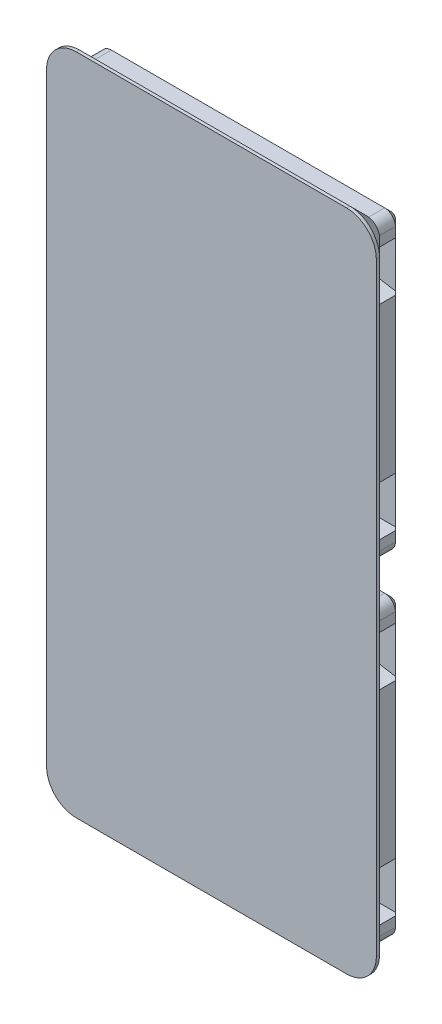
SolidWorks part; units mm, degrees
ref_plane "Front Plane" through (0, 0, 0) normal (0, 0, 1) x (1, 0, 0)
ref_plane "Top Plane" through (0, 0, 0) normal (0, 1, 0) x (1, 0, 0)
ref_plane "Right Plane" through (0, 0, 0) normal (1, 0, 0) x (0, 0, -1)
sketch "Sketch1" plane through (0, 0, 0) normal (0, 0, 1) x (1, 0, 0)
  line L1 (18.55, 18.55) -> (-18.55, 18.55)
  line L2 (18.55, 18.55) -> (18.55, -18.55)
  line L3 (18.55, -18.55) -> (-18.55, -18.55)
  line L4 (-18.55, 18.55) -> (-18.55, -18.55)
  line L5 (18.55, 18.55) -> (-18.55, -18.55) construction
  line L6 (18.55, -18.55) -> (-18.55, 18.55) construction
  point P0 (0, 0)
  dimension "D1" = 37.1
extrude "Boss-Extrude1" add sketch "Sketch1" along normal blind 2.6
sketch "Sketch2" plane through (0, 0, 2.6) normal (0, 0, 1) x (1, 0, 0)
  line L1 (-20.75, 20.75) -> (20.75, 20.75)
  line L2 (-20.75, 20.75) -> (-20.75, -20.75)
  line L3 (-20.75, -20.75) -> (20.75, -20.75)
  line L4 (20.75, 20.75) -> (20.75, -20.75)
  line L5 (-20.75, 20.75) -> (20.75, -20.75) construction
  line L6 (-20.75, -20.75) -> (20.75, 20.75) construction
  point P0 (0, 0)
  dimension "D1" = 41.5
extrude "Boss-Extrude2" add sketch "Sketch2" along normal blind 2.4
sketch "Sketch8" plane through (0, 0, 2.6) normal (0, 0, -1) x (-1, 0, 0)
  line L0 (-18.55, 18.55) -> (-18.55, 5.0094) construction
  line L1 (-18.55, -18.55) -> (-18.55, 18.55) construction
  line L2 (-14.8915, 10.3) -> (-18.55, 9.7)
  line L8 (12.7, 15.95) -> (-12.7, 15.95) construction
  line L9 (12.7, 9.45) -> (-12.7, 9.45) construction
  line L11 (-12.7, 15.95) -> (-18.55, 15.95)
  line L12 (-12.7, 12.7) -> (-12.7, -12.7)
  line L13 (-12.7, -12.7) -> (12.7, -12.7)
  line L14 (12.7, -12.7) -> (12.7, 12.7)
  line L15 (12.7, 12.7) -> (-12.7, 12.7)
  line L16 (-12.7, 9.45) -> (-12.7, -12.7) construction
  line L17 (-12.7, -12.7) -> (12.7, -12.7) construction
  line L18 (12.7, -12.7) -> (12.7, 12.7) construction
  line L19 (12.7, 12.7) -> (-12.7, 12.7) construction
  line L22 (-18.55, 15.95) -> (-18.55, 9.7)
  arc A0 (-12.7, 15.95) -> (-12.7, 9.45) centre (-12.7, 12.7) cw
  arc A1 (-12.7, 9.45) -> (-14.8915, 10.3) centre (-12.7, 12.7) cw
  dimension "D4" = 5.65
  dimension "D5" = 6.25
  dimension "D1" = 8.05
  dimension "D2" = 3.25
  dimension "D3" = 3.25
extrude "Base Magnet Slot" cut sketch "Sketch8" against normal blind 0.4 and the other way blind 2.2
fillet "Fillet1" radius 1.35 4 edges at (18.55, 18.55, 1.3) (18.55, -18.55, 1.3) (-18.55, -18.55, 1.3) (-18.55, 18.55, 1.3)
fillet "Fillet2" radius 3.75 4 edges at (20.75, -20.75, 3.8) (20.75, 20.75, 3.8) (-20.75, -20.75, 3.8) (-20.75, 20.75, 3.8)
chamfer "Chamfer1" distance 0.8 angle 45 8 edges at (-18.1546, 18.1546, 0) (-18.55, 0, 0) (-18.1546, -18.1546, 0) (0, -18.55, 0) (18.1546, -18.1546, 0) (18.55, 0, 0) (18.1546, 18.1546, 0) (0, 18.55, 0)
chamfer "Chamfer2" distance 2.4 angle 45 8 edges at (20.75, 0, 2.6) (19.6517, 19.6517, 2.6) (19.6517, -19.6517, 2.6) (0, 20.75, 2.6) (0, -20.75, 2.6) (-19.6517, 19.6517, 2.6) (-19.6517, -19.6517, 2.6) (-20.75, 0, 2.6)
mirror "Mirror1" about plane through (0, 0, 0) normal (0, 1, 0) of "Base Magnet Slot"
mirror "Mirror2" about plane through (0, 0, 0) normal (1, 0, 0) of "Mirror1"
sketch "Sketch14" plane through (0, 0, 0) normal (0, 0, -1) x (-1, 0, 0)
  line L0 (17.2, 17.75) -> (-17.2, 17.75) construction
  line L1 (-3, -15.75) -> (3, -15.75)
  line L2 (-3, -15.75) -> (-3, -3)
  line L3 (-3, 15.75) -> (3, 15.75)
  line L4 (3, -15.75) -> (3, -3)
  line L5 (-3, -15.75) -> (3, 15.75) construction
  line L6 (-3, 15.75) -> (3, -15.75) construction
  line L7 (-17.75, 17.2) -> (-17.75, -17.2) construction
  line L8 (-15.75, 3) -> (-3, 3)
  line L9 (-15.75, 3) -> (-15.75, -3)
  line L10 (-15.75, -3) -> (-3, -3)
  line L11 (15.75, 3) -> (15.75, -3)
  line L12 (-15.75, 3) -> (15.75, -3) construction
  line L13 (-15.75, -3) -> (15.75, 3) construction
  line L14 (-3, 3) -> (-3, 15.75)
  line L16 (3, 3) -> (15.75, 3)
  line L17 (3, 3) -> (3, 15.75)
  line L19 (3, -3) -> (15.75, -3)
  point P0 (0, 0)
  point P10 (0, 0)
  dimension "D1" = 6
  dimension "D2" = 2
  dimension "D3" = 2
extrude "Cut-Extrude2" cut sketch "Sketch14" against normal blind 3
fillet "Fillet4" radius 1 36 edges at (-9.375, -3, 0) (9.375, -3, 0) (-3, 9.375, 0) (-15.75, 0, 0) (0, -15.75, 0) (15.75, 0, 0) (0, 15.75, 0) (9.375, -3, 3) (-3, -9.375, 3) (-3, 9.375, 3) (3, 9.375, 3) (-9.375, 3, 0) (-3, -9.375, 0) (3, -9.375, 0) (9.375, 3, 0) (3, 9.375, 0) (0, -15.75, 3) (3, -9.375, 3) (3, -3, 1.5) (-15.75, 0, 3) (-9.375, -3, 3) (-9.375, 3, 3) (0, 15.75, 3) (9.375, 3, 3) (15.75, 0, 3) (-3, -3, 1.5) (-3, 3, 1.5) (3, 3, 1.5) (-15.75, 3, 1.5) (-15.75, -3, 1.5) (-3, -15.75, 1.5) (3, -15.75, 1.5) (15.75, -3, 1.5) (-3, 15.75, 1.5) (3, 15.75, 1.5) (15.75, 3, 1.5)
pattern_linear "LPattern1" count 2 spacing 42 along (0, -1, 0) of bodies 117
sketch "Sketch15" plane through (0, 0, 5) normal (0, 0, 1) x (1, 0, 0)
  line L0 (-17, -62.75) -> (17, -62.75) construction
  line L1 (20.75, -59) -> (20.75, -25) construction
  line L3 (-20.75, -25) -> (-20.75, -59) construction
  line L6 (17, 20.75) -> (-17, 20.75) construction
  line L8 (-17, -62.75) -> (17, -62.75)
  line L9 (20.75, -59) -> (20.75, 17)
  line L11 (-20.75, 17) -> (-20.75, -59)
  line L14 (17, 20.75) -> (-17, 20.75)
  arc A0 (17, -62.75) -> (20.75, -59) centre (17, -59) ccw construction
  arc A3 (-20.75, -59) -> (-17, -62.75) centre (-17, -59) ccw construction
  arc A5 (20.75, 17) -> (17, 20.75) centre (17, 17) ccw construction
  arc A6 (-17, 20.75) -> (-20.75, 17) centre (-17, 17) ccw construction
  arc A8 (17, -62.75) -> (20.75, -59) centre (17, -59) ccw
  arc A11 (-20.75, -59) -> (-17, -62.75) centre (-17, -59) ccw
  arc A13 (20.75, 17) -> (17, 20.75) centre (17, 17) ccw
  arc A14 (-17, 20.75) -> (-20.75, 17) centre (-17, 17) ccw
extrude "Boss-Extrude3" add sketch "Sketch15" along normal blind 0.4
